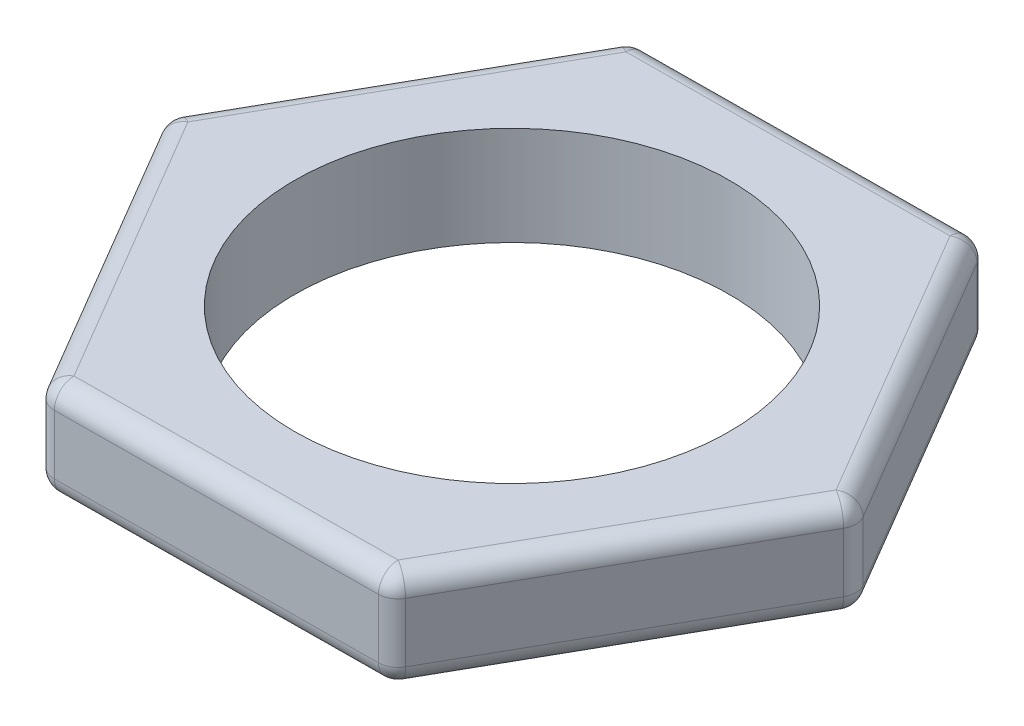
SolidWorks part; units mm, degrees
ref_plane "Front Plane" through (0, 0, 0) normal (0, 0, 1) x (1, 0, 0)
ref_plane "Top Plane" through (0, 0, 0) normal (0, 1, 0) x (1, 0, 0)
ref_plane "Right Plane" through (0, 0, 0) normal (1, 0, 0) x (0, 0, -1)
sketch "Sketch1" plane through (0, 0, 0) normal (0, 1, 0) x (1, 0, 0)
  line L1 (8.8302, -15) -> (17.4055, 0.1472)
  line L2 (17.4055, 0.1472) -> (8.5753, 15.1472)
  line L3 (8.5753, 15.1472) -> (-8.8302, 15)
  line L4 (-8.8302, 15) -> (-17.4055, -0.1472)
  line L5 (-17.4055, -0.1472) -> (-8.5753, -15.1472)
  line L6 (-8.5753, -15.1472) -> (8.8302, -15)
  circle A0 centre (0, 0) radius 11
  circle A1 centre (0, 0) radius 15.0741 construction
  circle A2 centre (0, 0) radius 15.0741 construction
extrude "Boss-Extrude1" add sketch "Sketch1" along normal blind 5
fillet "Fillet1" radius 1 6 edges at (-12.9904, 0, 7.6472) (-13.1178, 0, -7.4264) (-0.1274, 0, -15.0736) (12.9904, 0, -7.6472) (13.1178, 0, 7.4264) (0.1274, 0, 15.0736)
fillet "Fillet2" radius 1 6 edges at (12.9904, 5, -7.6472) (-0.1274, 5, -15.0736) (-13.1178, 5, -7.4264) (-12.9904, 5, 7.6472) (0.1274, 5, 15.0736) (13.1178, 5, 7.4264)
fillet "Fillet3" radius 1 3 edges at (8.6586, 0.2929, 14.7085) (8.8302, 2.5, 15) (8.6586, 4.7071, 14.7085)
fillet "Fillet4" radius 1 3 edges at (-8.4087, 0.2929, 14.8528) (-8.5753, 2.5, 15.1472) (-8.4087, 4.7071, 14.8528)
fillet "Fillet5" radius 1 3 edges at (-17.0673, 0.2929, 0.1443) (-17.4055, 2.5, 0.1472) (-17.0673, 4.7071, 0.1443)
fillet "Fillet6" radius 1 3 edges at (-8.6586, 0.2929, -14.7085) (-8.8302, 2.5, -15) (-8.6586, 4.7071, -14.7085)
fillet "Fillet7" radius 1 3 edges at (8.4087, 0.2929, -14.8528) (8.5753, 2.5, -15.1472) (8.4087, 4.7071, -14.8528)
fillet "Fillet8" radius 1 3 edges at (17.0673, 0.2929, -0.1443) (17.4055, 2.5, -0.1472) (17.0673, 4.7071, -0.1443)
